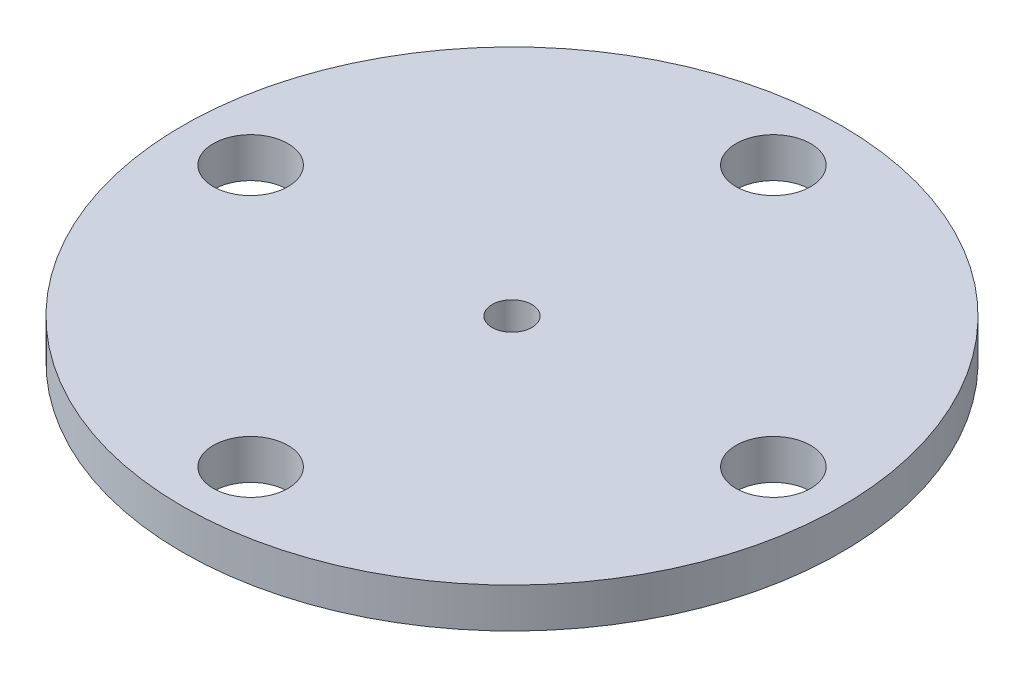
SolidWorks part; units mm, degrees
material "1060 Alloy"
ref_plane "Front Plane" through (0, 0, 0) normal (0, 0, 1) x (1, 0, 0)
ref_plane "Top Plane" through (0, 0, 0) normal (0, 1, 0) x (1, 0, 0)
ref_plane "Right Plane" through (0, 0, 0) normal (1, 0, 0) x (0, 0, -1)
sketch "Sketch1" plane through (0, 0, 0) normal (0, 1, 0) x (1, 0, 0)
  circle A0 centre (0, 0) radius 66.2
  circle A1 centre (0, 0) radius 4
  dimension "D1" = 132.4
  dimension "D2" = 8
extrude "Boss-Extrude2" add sketch "Sketch1" along normal blind 8 contours A0 A1 region at (-64.3276, 0, 0)
sketch "Sketch2" plane through (0, 8, 0) normal (0, 1, 0) x (1, 0, 0)
  circle A0 centre (0, 0) radius 52.5 construction
  circle A1 centre (0, -52.5) radius 7.5
  circle A2 centre (-52.5, 0) radius 7.5
  circle A3 centre (0, 52.5) radius 7.5
  circle A4 centre (52.5, 0) radius 7.5
  point P14 (0, 0)
  dimension "D1" = 105
  dimension "D2" = 15
  dimension "D3" = 4
extrude "Cut-Extrude1" cut sketch "Sketch2" against normal through all
